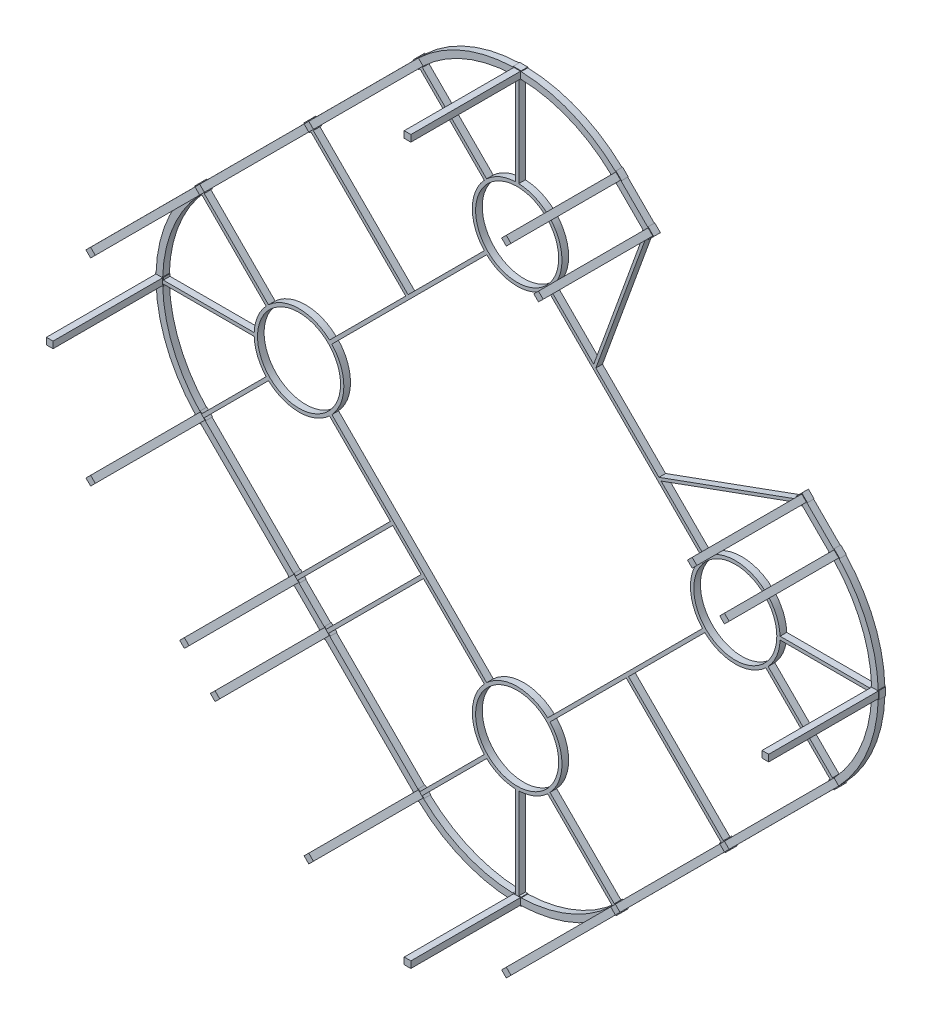
SolidWorks part; units mm, degrees
material "PET"
ref_plane "Front Plane" through (0, 0, 0) normal (0, 0, 1) x (1, 0, 0)
ref_plane "Top Plane" through (0, 0, 0) normal (0, 1, 0) x (1, 0, 0)
ref_plane "Right Plane" through (0, 0, 0) normal (1, 0, 0) x (0, 0, -1)
sketch "Sketch1" plane through (0, 0, 0) normal (0, 0, 1) x (1, 0, 0)
  line L96 (-31.2949, 95.2721) -> (-62.435, 64.132)
  line L97 (-95.2719, -31.2952) -> (-68.7516, -57.8154)
  line L98 (95.2742, -31.2929) -> (64.132, -62.435)
  line L99 (31.2931, 95.274) -> (39.3012, 87.2658)
  line L102 (95.4168, -28.0415) -> (95.5445, -28.1692)
  line L103 (-62.5717, 60.8746) -> (-62.7178, 61.0208)
  line L105 (-60.8746, 62.5717) -> (-61.0208, 62.7178)
  line L108 (-106.5251, 1.2) -> (-106.7143, 1.2)
  line L110 (-106.5251, -1.2) -> (-106.7143, -1.2)
  line L111 (-1.2, -106.5251) -> (-1.2, -106.7143)
  line L112 (1.2, -106.5251) -> (1.2, -106.7143)
  line L113 (60.8746, -62.5717) -> (61.0208, -62.7178)
  line L114 (62.5717, -60.8746) -> (62.7178, -61.0208)
  line L115 (106.5251, -1.2) -> (106.7143, -1.2)
  line L118 (106.5251, 1.2) -> (106.7143, 1.2)
  line L121 (93.7188, 29.7348) -> (93.8631, 29.8791)
  line L122 (95.4159, 28.0378) -> (95.5458, 28.1677)
  line L123 (29.7354, 93.7161) -> (29.8789, 93.8597)
  line L124 (28.0383, 95.4131) -> (28.1694, 95.5443)
  line L125 (-1.2, 106.5251) -> (-1.2, 106.7143)
  line L126 (1.2, 106.5251) -> (1.2, 106.7143)
  line L127 (93.7198, -29.7386) -> (93.8599, -29.8787)
  line L128 (-106.7272, -1) -> (-108.7272, -1)
  line L137 (-106.7272, 1) -> (-108.7272, 1)
  line L138 (-95.411, 28.3121) -> (-96.8252, 29.7262)
  line L139 (-93.9969, 29.7264) -> (-95.4111, 31.1406)
  line L140 (-93.7194, 29.7317) -> (-93.8631, 29.8755)
  line L141 (-95.4164, 28.0346) -> (-95.5476, 28.1659)
  line L142 (-61.1589, 62.5731) -> (-62.5731, 63.9873)
  line L143 (-62.5731, 61.1589) -> (-63.9874, 62.5731)
  line L144 (-28.3184, 95.4068) -> (-29.7326, 96.821)
  line L145 (-28.041, 95.4122) -> (-28.1713, 95.5425)
  line L146 (-29.7327, 93.9927) -> (-31.1469, 95.4069)
  line L147 (-29.738, 93.7152) -> (-29.8807, 93.8579)
  line L149 (-1, 106.7272) -> (-1, 108.7272)
  line L150 (1, 106.7272) -> (1, 108.7272)
  line L152 (28.3157, 95.4078) -> (29.7299, 96.822)
  line L153 (29.73, 93.9937) -> (31.1442, 95.4079)
  line L154 (39.4263, 84.2797) -> (40.8406, 85.6939)
  line L155 (38.0121, 85.6939) -> (39.4263, 87.1081)
  line L156 (37.7278, 85.6924) -> (37.887, 85.8516)
  line L157 (84.282, 39.4255) -> (85.6962, 40.8397)
  line L158 (85.6948, 37.727) -> (85.8547, 37.8869)
  line L159 (85.6963, 38.0113) -> (87.1105, 39.4256)
  line L160 (93.9963, 29.7295) -> (95.4105, 31.1437)
  line L161 (95.4105, 28.3152) -> (96.8247, 29.7294)
  line L162 (106.7272, -1) -> (108.7272, -1)
  line L163 (106.7272, 1) -> (108.7272, 1)
  line L164 (93.9973, -29.7332) -> (95.4116, -31.1474)
  line L165 (95.4114, -28.3189) -> (96.8257, -29.7331)
  line L166 (62.5731, -61.1589) -> (63.9874, -62.5731)
  line L167 (61.1589, -62.5731) -> (62.5731, -63.9873)
  line L168 (29.7331, -93.9995) -> (31.1473, -95.4137)
  line L169 (28.3189, -95.4137) -> (29.7331, -96.8279)
  line L170 (-1, -106.7272) -> (-1, -108.7272)
  line L179 (1, -106.7272) -> (1, -108.7272)
  line L180 (-29.7296, -94.0005) -> (-31.1438, -95.4148)
  line L181 (-28.3153, -95.4146) -> (-29.7294, -96.8289)
  line L182 (-56.5346, -67.1881) -> (-57.9488, -68.6023)
  line L183 (-57.9488, -65.7738) -> (-59.3631, -67.1881)
  line L184 (-67.188, -56.5346) -> (-68.6023, -57.9489)
  line L185 (-65.7738, -57.9489) -> (-67.188, -59.3631)
  line L186 (-95.4154, -28.0446) -> (-95.5423, -28.1715)
  line L187 (-95.41, -28.3221) -> (-96.8243, -29.7363)
  line L188 (-93.9959, -29.7363) -> (-95.4101, -31.1505)
  line L189 (-93.7184, -29.7417) -> (-93.8577, -29.8809)
  line L190 (0, 65.6738) -> (29.0324, 94.7062) construction
  line L191 (0, 65.6738) -> (0, 106.7318) construction
  line L192 (0, 65.6738) -> (-9.5459, 75.2198) construction
  line L193 (27.2253, 93.6061) -> (27.9324, 92.899) construction
  line L194 (-0.5, 103.688) -> (0.5, 103.688) construction
  line L195 (94.9235, -28.5426) -> (75.5667, -9.1858)
  line L196 (29.2463, 94.213) -> (9.8929, 74.8596)
  line L197 (28.5392, 94.9201) -> (9.1858, 75.5667)
  line L198 (94.2164, -29.2497) -> (74.8596, -9.8929)
  line L199 (0.5, 106.5306) -> (0.5, 79.1645)
  line L200 (-0.5, 106.5306) -> (-0.5, 79.1645)
  line L201 (1.2, 108.7151) -> (1.2, 108.9252)
  line L202 (106.5306, -0.5) -> (79.1645, -0.5)
  line L203 (106.5306, 0.5) -> (79.1645, 0.5)
  line L204 (-28.5399, 94.9212) -> (-9.1858, 75.5667)
  line L205 (-29.2471, 94.2139) -> (-9.8928, 74.8597)
  line L206 (94.9214, 28.5401) -> (75.5667, 9.1858)
  line L207 (94.2141, 29.2473) -> (74.8597, 9.8928)
  line L208 (-28.5424, -94.9233) -> (-9.1858, -75.5667)
  line L209 (-29.2495, -94.2162) -> (-9.8929, -74.8596)
  line L210 (-0.5, -106.5306) -> (-0.5, -79.1645)
  line L211 (0.5, -106.5306) -> (0.5, -79.1645)
  line L212 (28.5435, -94.9248) -> (9.1858, -75.5667)
  line L213 (29.2507, -94.2176) -> (9.8928, -74.8597)
  line L214 (-94.9199, 28.539) -> (-75.5667, 9.1858)
  line L223 (-94.2127, 29.2461) -> (-74.8596, 9.8929)
  line L224 (-106.5306, 0.5) -> (-79.1645, 0.5)
  line L225 (-106.5306, -0.5) -> (-79.1645, -0.5)
  line L226 (-94.9246, -28.5433) -> (-75.5667, -9.1858)
  line L227 (-94.2174, -29.2505) -> (-74.8597, -9.8928)
  line L228 (0, 65.6738) -> (-65.6738, 0) construction
  line L229 (-34.1935, 32.1874) -> (-33.4863, 31.4803) construction
  line L230 (-33.4863, 31.4803) -> (-55.7808, 9.1858)
  line L231 (-34.1935, 32.1874) -> (-56.4879, 9.8929)
  line L232 (-34.1935, 32.1874) -> (-33.544, 32.8369)
  line L233 (-33.4863, 31.4803) -> (-9.1858, 55.7808)
  line L234 (-32.8369, 32.8369) -> (-61.8693, 61.8693) construction
  line L235 (-32.8369, 33.544) -> (-9.8929, 56.4879)
  line L236 (-32.8369, 33.544) -> (-61.3735, 62.0806)
  line L237 (-33.544, 32.8369) -> (-62.0806, 61.3735)
  line L238 (0, 0) -> (35.109, 35.109) construction
  line L239 (31.4803, -33.4863) -> (9.1858, -55.7808)
  line L240 (32.1874, -34.1935) -> (9.8929, -56.4879)
  line L241 (31.4803, -33.4863) -> (55.7808, -9.1858)
  line L242 (32.1874, -34.1935) -> (32.8369, -33.544)
  line L243 (33.544, -32.8369) -> (62.0806, -61.3735)
  line L244 (32.8369, -33.544) -> (61.3735, -62.0806)
  line L245 (-96.9625, 29.5806) -> (-97.1135, 29.7317)
  line L246 (-38.1636, -28.2173) -> (-56.4879, -9.8929)
  line L247 (56.4879, 9.8929) -> (43.3373, 23.0436)
  line L248 (-66.4842, -57.245) -> (-37.81, -28.5708) construction
  line L249 (-52.5007, -42.5544) -> (-51.7936, -43.2615) construction
  line L250 (-28.2173, -38.1636) -> (-56.7492, -66.6955)
  line L251 (-28.9244, -37.4565) -> (-57.4563, -65.9884)
  line L252 (-37.4565, -28.9244) -> (-65.9884, -57.4563)
  line L253 (-38.1636, -28.2173) -> (-66.6955, -56.7492)
  line L254 (-65.4895, -57.9474) -> (-65.6404, -58.0982)
  line L255 (-67.1866, -56.2503) -> (-67.3374, -56.4012)
  line L256 (-57.9474, -65.4895) -> (-58.0982, -65.6404)
  line L257 (-56.2503, -67.1866) -> (-56.4012, -67.3374)
  line L258 (-29.7349, -93.723) -> (-29.8753, -93.8633)
  line L259 (-28.0378, -95.42) -> (-28.1656, -95.5478)
  line L260 (28.0414, -95.4191) -> (28.168, -95.5456)
  line L261 (29.7385, -93.722) -> (29.8775, -93.8611)
  line L262 (-55.7808, -9.1859) -> (-9.1859, -55.7809)
  line L263 (-28.9244, -37.4565) -> (-37.4565, -28.9244)
  line L264 (-9.8929, -56.4879) -> (-28.2173, -38.1636)
  line L265 (9.1859, 55.7809) -> (55.7808, 9.1859)
  line L266 (-95.2774, 31.2897) -> (-95.4165, 31.4288)
  line L267 (-93.8631, 29.8755) -> (-62.7178, 61.0208)
  line L268 (-96.1204, 30.4466) -> (-95.4111, 31.1406)
  line L269 (-95.411, 28.3121) -> (-93.9969, 29.7264)
  line L270 (-61.0208, 62.7178) -> (-29.8807, 93.8579)
  line L271 (-62.435, 64.132) -> (-62.5717, 64.2688)
  line L272 (-64.132, 62.435) -> (-95.2774, 31.2897)
  line L273 (-64.132, 62.435) -> (-64.2688, 62.5717)
  line L274 (-62.5764, 61.1622) -> (-61.1622, 62.5764)
  line L275 (-63.9874, 62.5731) -> (-62.5731, 63.9873)
  line L276 (-31.2949, 95.2721) -> (-31.4351, 95.4123)
  line L277 (-29.5861, 96.9573) -> (-29.7381, 97.1093)
  line L278 (-31.1469, 95.4069) -> (-29.7326, 96.821)
  line L279 (-29.7327, 93.9927) -> (-28.3184, 95.4068)
  line L280 (-1.2, 108.7151) -> (-1.2, 108.9252)
  line L281 (-1, 106.7272) -> (1, 106.7272)
  line L282 (29.5841, 96.9591) -> (29.7353, 97.1103)
  line L283 (31.2931, 95.274) -> (31.4324, 95.4133)
  line L284 (29.8789, 93.8597) -> (37.887, 85.8516)
  line L285 (28.3157, 95.4078) -> (29.73, 93.9937)
  line L286 (29.7299, 96.822) -> (31.1442, 95.4079)
  line L287 (39.3012, 87.2658) -> (39.4249, 87.3895)
  line L288 (38.0121, 85.6939) -> (39.4263, 84.2797)
  line L289 (40.8406, 85.6939) -> (39.4263, 87.1081)
  line L290 (87.2674, 39.2997) -> (87.3919, 39.4242)
  line L291 (87.2674, 39.2997) -> (95.2755, 31.2915)
  line L292 (85.8547, 37.8869) -> (93.8631, 29.8791)
  line L293 (84.282, 39.4255) -> (85.6963, 38.0113)
  line L294 (85.6962, 40.8397) -> (87.1105, 39.4256)
  line L295 (93.9963, 29.7295) -> (95.4105, 28.3152)
  line L296 (96.8247, 29.7294) -> (95.4105, 31.1437)
  line L297 (95.2755, 31.2915) -> (95.4159, 31.4319)
  line L298 (96.9606, 29.5825) -> (97.113, 29.7349)
  line L299 (108.7151, 1.2) -> (108.9252, 1.2)
  line L300 (108.7151, -1.2) -> (108.9252, -1.2)
  line L301 (106.7272, -1) -> (106.7272, 1)
  line L302 (93.8599, -29.8787) -> (62.7178, -61.0208)
  line L303 (93.9973, -29.7332) -> (95.4114, -28.3189)
  line L304 (95.4116, -31.1474) -> (96.8257, -29.7331)
  line L305 (96.9593, -29.5839) -> (97.1139, -29.7385)
  line L306 (95.2742, -31.2929) -> (95.4169, -31.4356)
  line L307 (64.132, -62.435) -> (64.2688, -62.5717)
  line L308 (62.435, -64.132) -> (62.5717, -64.2688)
  line L309 (61.0208, -62.7178) -> (29.8775, -93.8611)
  line L310 (62.435, -64.132) -> (31.2917, -95.2753)
  line L311 (62.5764, -61.1622) -> (61.1622, -62.5764)
  line L312 (62.5731, -63.9873) -> (63.9874, -62.5731)
  line L313 (31.2917, -95.2753) -> (31.4356, -95.4191)
  line L314 (29.5828, -96.9604) -> (29.7385, -97.1162)
  line L315 (28.3189, -95.4137) -> (29.7331, -93.9995)
  line L316 (29.7331, -96.8279) -> (31.1473, -95.4137)
  line L317 (1.2, -108.7151) -> (1.2, -108.9252)
  line L318 (-1.2, -108.7151) -> (-1.2, -108.9252)
  line L319 (-1, -106.7272) -> (1, -106.7272)
  line L320 (-29.5804, -96.9627) -> (-29.7349, -97.1171)
  line L321 (-31.2894, -95.2776) -> (-31.432, -95.4201)
  line L322 (-29.7296, -94.0005) -> (-28.3153, -95.4146)
  line L323 (-29.7294, -96.8289) -> (-31.1438, -95.4148)
  line L324 (-57.9488, -65.7738) -> (-56.5346, -67.1881)
  line L325 (-56.4012, -67.3374) -> (-29.8753, -93.8633)
  line L326 (-57.8154, -68.7516) -> (-31.2894, -95.2776)
  line L327 (-59.5124, -67.0546) -> (-59.6445, -67.1866)
  line L328 (-57.8154, -68.7516) -> (-57.9474, -68.8837)
  line L329 (-57.9488, -68.6023) -> (-59.3631, -67.1881)
  line L330 (-68.7516, -57.8154) -> (-68.8837, -57.9474)
  line L331 (-67.0546, -59.5124) -> (-67.1866, -59.6445)
  line L332 (-65.6404, -58.0982) -> (-58.0982, -65.6404)
  line L333 (-68.6023, -57.9489) -> (-67.188, -59.3631)
  line L334 (-67.0546, -59.5124) -> (-59.5124, -67.0546)
  line L335 (-67.188, -56.5346) -> (-65.7738, -57.9489)
  line L336 (-96.9571, -29.5863) -> (-97.1125, -29.7417)
  line L337 (-93.8577, -29.8809) -> (-67.3374, -56.4012)
  line L338 (-95.41, -28.3221) -> (-93.9959, -29.7363)
  line L339 (-95.4101, -31.1505) -> (-96.8243, -29.7363)
  line L340 (-95.2719, -31.2952) -> (-95.4155, -31.4388)
  line L341 (-108.7151, -1.2) -> (-108.9252, -1.2)
  line L342 (-108.7151, 1.2) -> (-108.9252, 1.2)
  line L343 (-108.7272, -1) -> (-108.7272, 1)
  line L344 (-106.7272, 1) -> (-106.7272, -1)
  line L345 (108.7272, 1) -> (108.7272, -1)
  line L346 (33.544, -32.8369) -> (56.4879, -9.8929)
  line L347 (38.5811, 84.8487) -> (23.3679, 43.013) construction
  line L348 (37.9483, 84.3245) -> (38.7294, 84.0405) construction
  line L349 (37.9483, 84.3245) -> (38.2564, 85.1719)
  line L350 (38.2564, 85.1719) -> (23.0436, 43.3373)
  line L351 (39.4249, 83.9954) -> (41.122, 85.6925)
  line L352 (83.9977, 39.424) -> (85.6948, 41.1212)
  line L353 (38.905, 84.5233) -> (23.6922, 42.6887)
  line L354 (85.1719, 38.2564) -> (43.3373, 23.0436)
  line L355 (84.5233, 38.905) -> (42.6887, 23.6922)
  line L356 (42.6887, 23.6922) -> (23.6922, 42.6887)
  line L357 (23.0436, 43.3373) -> (9.8929, 56.4879)
  line L358 (83.9977, 39.424) -> (84.5233, 38.905)
  line L359 (85.1719, 38.2564) -> (85.6948, 37.727)
  arc A156 (-96.1204, 30.4466) -> (-96.8247, 29.7257) centre (-65.6738, 0) ccw
  arc A157 (-28.1656, -95.5478) -> (-1.2, -106.7143) centre (0, -65.6738) ccw
  arc A158 (95.5445, -28.1692) -> (106.7143, -1.2) centre (65.6738, 0) ccw
  arc A159 (29.5841, 96.9591) -> (1.2, 108.7151) centre (0, 65.6738) ccw
  arc A160 (28.1694, 95.5443) -> (1.2, 106.7143) centre (0, 65.6738) ccw
  arc A161 (95.4169, -31.4356) -> (97.1139, -29.7385) centre (18.534, 47.1392) ccw
  arc A162 (-60.8746, 62.5717) -> (-61.3735, 62.0806) centre (14.3086, -14.3086) ccw
  arc A163 (-62.5717, 64.2688) -> (-64.2688, 62.5717) centre (14.3086, -14.3086) ccw
  arc A164 (-108.9252, 1.2) -> (-108.9252, -1.2) centre (1, 0) ccw
  arc A165 (-106.5251, 1.2) -> (-106.5306, 0.5) centre (1, 0) ccw
  arc A166 (-1.2, -106.5251) -> (-0.5, -106.5306) centre (0, 1) ccw
  arc A167 (-1.2, -108.9252) -> (1.2, -108.9252) centre (0, 1) ccw
  arc A168 (60.8746, -62.5717) -> (61.3735, -62.0806) centre (-14.3086, 14.3086) ccw
  arc A169 (62.5717, -64.2688) -> (64.2688, -62.5717) centre (-14.3086, 14.3086) ccw
  arc A170 (106.5251, -1.2) -> (106.5306, -0.5) centre (-1, 0) ccw
  arc A171 (108.9252, -1.2) -> (108.9252, 1.2) centre (-1, 0) ccw
  arc A172 (95.4159, 28.0378) -> (94.9214, 28.5401) centre (18.5356, -47.1454) ccw
  arc A173 (97.113, 29.7349) -> (95.4159, 31.4319) centre (18.5356, -47.1454) ccw
  arc A174 (29.7354, 93.7161) -> (29.2463, 94.213) centre (-47.1424, 18.5304) ccw
  arc A175 (31.4324, 95.4133) -> (29.7353, 97.1103) centre (-47.1424, 18.5304) ccw
  arc A176 (1.2, 106.5251) -> (0.5, 106.5306) centre (0, -1) ccw
  arc A177 (1.2, 108.9252) -> (-1.2, 108.9252) centre (0, -1) ccw
  arc A178 (93.7198, -29.7386) -> (94.2164, -29.2497) centre (18.534, 47.1392) ccw
  arc A179 (-93.7194, 29.7317) -> (-94.2127, 29.2461) centre (-18.5336, -47.1461) ccw
  arc A180 (-95.4165, 31.4288) -> (-97.1135, 29.7317) centre (-18.5336, -47.1461) ccw
  arc A181 (-28.041, 95.4122) -> (-28.5399, 94.9212) centre (47.1422, 18.532) ccw
  arc A182 (-29.7381, 97.1093) -> (-31.4351, 95.4123) centre (47.1422, 18.532) ccw
  arc A183 (39.4249, 83.9954) -> (38.905, 84.5233) centre (-37.4554, 8.8122) ccw
  arc A184 (41.122, 85.6925) -> (39.4249, 87.3895) centre (-37.4554, 8.8122) ccw
  arc A185 (87.3919, 39.4242) -> (85.6948, 41.1212) centre (8.8171, -37.4587) ccw
  arc A186 (-97.1125, -29.7417) -> (-95.4155, -31.4388) centre (-18.5352, 47.1386) ccw
  arc A187 (-95.4154, -28.0446) -> (-94.9246, -28.5433) centre (-18.5352, 47.1386) ccw
  circle A188 centre (0, 65.6738) radius 12.5
  arc A189 (-9.1858, 55.7808) -> (9.1859, 55.7809) centre (0, 65.6738) ccw
  arc A190 (79.1645, 0.5) -> (75.5667, 9.1858) centre (65.6738, 0) ccw
  circle A191 centre (65.6738, 0) radius 12.5
  arc A192 (9.1858, -55.7808) -> (-9.1859, -55.7809) centre (0, -65.6738) ccw
  circle A193 centre (0, -65.6738) radius 12.5
  arc A194 (-55.7808, -9.1859) -> (-55.7808, 9.1858) centre (-65.6738, 0) ccw
  circle A195 centre (-65.6738, 0) radius 12.5
  arc A196 (-68.8837, -57.9474) -> (-67.1866, -59.6445) centre (9.6937, 18.9329) ccw
  arc A197 (-67.1866, -56.2503) -> (-66.6955, -56.7492) centre (9.6937, 18.9329) ccw
  arc A198 (-59.6445, -67.1866) -> (-57.9474, -68.8837) centre (18.9329, 9.6937) ccw
  arc A199 (-57.9474, -65.4895) -> (-57.4563, -65.9884) centre (18.9329, 9.6937) ccw
  arc A200 (-31.432, -95.4201) -> (-29.7349, -97.1171) centre (47.1428, -18.5372) ccw
  arc A201 (-29.7349, -93.723) -> (-29.2495, -94.2162) centre (47.1428, -18.5372) ccw
  arc A202 (28.0414, -95.4191) -> (28.5435, -94.9248) centre (-47.1418, -18.5388) ccw
  arc A203 (29.7385, -97.1162) -> (31.4356, -95.4191) centre (-47.1418, -18.5388) ccw
  arc A204 (-96.9625, 29.5806) -> (-108.7151, 1.2) centre (-65.6738, 0) ccw
  arc A205 (-95.5476, 28.1659) -> (-106.7143, 1.2) centre (-65.6738, 0) ccw
  arc A206 (-94.9199, 28.539) -> (-95.4164, 28.0346) centre (-18.5336, -47.1461) ccw
  arc A207 (-62.0806, 61.3735) -> (-62.5717, 60.8746) centre (14.3086, -14.3086) ccw
  arc A208 (-29.2471, 94.2139) -> (-29.738, 93.7152) centre (47.1422, 18.532) ccw
  arc A209 (-1.2, 108.7151) -> (-29.5861, 96.9573) centre (0, 65.6738) ccw
  arc A210 (1, 108.7202) -> (-1, 108.7202) centre (0, 65.6738) ccw
  arc A211 (28.5392, 94.9201) -> (28.0383, 95.4131) centre (-47.1424, 18.5304) ccw
  arc A212 (-1.2, 106.7143) -> (-28.1713, 95.5425) centre (0, 65.6738) ccw
  arc A213 (-0.5, 106.5306) -> (-1.2, 106.5251) centre (0, -1) ccw
  arc A214 (94.2141, 29.2473) -> (93.7188, 29.7348) centre (18.5356, -47.1454) ccw
  arc A215 (75.5667, -9.1858) -> (79.1645, -0.5) centre (65.6738, 0) ccw
  arc A216 (108.7151, 1.2) -> (96.9606, 29.5825) centre (65.6738, 0) ccw
  arc A217 (106.7143, 1.2) -> (95.5458, 28.1677) centre (65.6738, 0) ccw
  arc A218 (106.5306, 0.5) -> (106.5251, 1.2) centre (-1, 0) ccw
  arc A219 (94.9235, -28.5426) -> (95.4168, -28.0415) centre (18.534, 47.1392) ccw
  arc A220 (96.9593, -29.5839) -> (108.7151, -1.2) centre (65.6738, 0) ccw
  arc A221 (62.0806, -61.3735) -> (62.5717, -60.8746) centre (-14.3086, 14.3086) ccw
  arc A222 (29.2507, -94.2176) -> (29.7385, -93.722) centre (-47.1418, -18.5388) ccw
  arc A223 (0.5, -106.5306) -> (1.2, -106.5251) centre (0, 1) ccw
  arc A224 (1.2, -106.7143) -> (28.168, -95.5456) centre (0, -65.6738) ccw
  arc A225 (-1, -108.7202) -> (1, -108.7202) centre (0, -65.6738) ccw
  arc A226 (1.2, -108.7151) -> (29.5828, -96.9604) centre (0, -65.6738) ccw
  arc A227 (-28.5424, -94.9233) -> (-28.0378, -95.42) centre (47.1428, -18.5372) ccw
  arc A228 (-29.5804, -96.9627) -> (-1.2, -108.7151) centre (0, -65.6738) ccw
  arc A229 (-56.7492, -66.6955) -> (-56.2503, -67.1866) centre (18.9329, 9.6937) ccw
  arc A230 (-65.9884, -57.4563) -> (-65.4895, -57.9474) centre (9.6937, 18.9329) ccw
  arc A231 (-94.2174, -29.2505) -> (-93.7184, -29.7417) centre (-18.5352, 47.1386) ccw
  arc A232 (-106.7143, -1.2) -> (-95.5423, -28.1715) centre (-65.6738, 0) ccw
  arc A233 (-106.5306, -0.5) -> (-106.5251, -1.2) centre (1, 0) ccw
  arc A234 (-108.7151, -1.2) -> (-96.9571, -29.5863) centre (-65.6738, 0) ccw
  arc A235 (56.4879, -9.8929) -> (74.8596, -9.8929) centre (65.6738, 0) ccw
  arc A236 (55.7808, 9.1859) -> (55.7808, -9.1858) centre (65.6738, 0) ccw
  arc A237 (74.8597, 9.8928) -> (56.4879, 9.8929) centre (65.6738, 0) ccw
  arc A238 (9.8928, -74.8597) -> (9.8929, -56.4879) centre (0, -65.6738) ccw
  arc A239 (0.5, -79.1645) -> (9.1858, -75.5667) centre (0, -65.6738) ccw
  arc A240 (-9.1858, -75.5667) -> (-0.5, -79.1645) centre (0, -65.6738) ccw
  arc A241 (-9.8929, -56.4879) -> (-9.8929, -74.8596) centre (0, -65.6738) ccw
  arc A242 (-74.8597, -9.8928) -> (-56.4879, -9.8929) centre (-65.6738, 0) ccw
  arc A243 (-79.1645, -0.5) -> (-75.5667, -9.1858) centre (-65.6738, 0) ccw
  arc A244 (-75.5667, 9.1858) -> (-79.1645, 0.5) centre (-65.6738, 0) ccw
  arc A245 (-56.4879, 9.8929) -> (-74.8596, 9.8929) centre (-65.6738, 0) ccw
  arc A246 (9.8929, 56.4879) -> (9.8929, 74.8596) centre (0, 65.6738) ccw
  arc A247 (9.1858, 75.5667) -> (0.5, 79.1645) centre (0, 65.6738) ccw
  arc A248 (-0.5, 79.1645) -> (-9.1858, 75.5667) centre (0, 65.6738) ccw
  arc A249 (-9.8928, 74.8597) -> (-9.8929, 56.4879) centre (0, 65.6738) ccw
  arc A250 (38.2564, 85.1719) -> (37.7278, 85.6924) centre (-37.4554, 8.8122) ccw
  point P157 (27.5788, 93.2526)
  point P165 (0, 103.688)
  point P224 (-33.8399, 31.8339)
  point P233 (-32.8369, 32.8369)
  point P252 (-52.1471, -42.9079)
  point P294 (38.3389, 84.1825)
  dimension "D1" = 25
  dimension "D2" = 1
  dimension "D3" = 1
  dimension "D4" = 1
  dimension "D5" = 1
  dimension "D6" = 6.0331
  dimension "D7" = 1
  dimension "D8" = 0.8312
extrude "Boss-Extrude1" add sketch "Sketch1" against normal blind 2 contours L293 | L303 | L180 | L335 region at (-31.1472, 95.56, 0) region at (85.6962, 39.4255, 0) region at (-29.7295, -95.4147, 0)
extrude "Boss-Extrude2" add sketch "Sketch1<4>" along normal blind 35 from offset 2 contours L268 A156 L138 L269 L139 | L275 L143 L274 L142 | L146 L279 L144 L278 | L150 A210 L149 L281 | L286 L152 L285 L153 | L154 L289 L155 L288 | L294 L157 L293 L159 | L161 L296 L160 L295 | L345 L163 L301 L162 | L164 L304 L165 L303 | L167 L312 L166 L311 | L169 L316 L168 L315 | L170 A225 L179 L319 | L323 L181 L322 L180 | L329 L182 L324 L183 | L335 L184 L333 L185 | L339 L188 L338 L187 | L344 L137 L343 L128 region at (-107.7272, 0, 0) region at (-95.4134, 29.7284, 0) region at (-62.5748, 62.5748, 0) region at (-29.7327, 95.4069, 0) region at (0, 107.7276, 0) region at (29.73, 95.4078, 0) region at (39.4263, 85.6939, 0) region at (85.6962, 39.4255, 0) region at (95.4105, 29.7295, 0) region at (107.7272, 0, 0) region at (95.4115, -29.7332, 0) region at (62.5748, -62.5748, 0) region at (29.7331, -95.4137, 0) region at (0, -107.7276, 0) region at (-29.7295, -95.4147, 0) region at (-57.9488, -67.1881, 0) region at (-67.188, -57.9489, 0) region at (-95.4101, -29.7363, 0) offset against normal yes
sketch "Sketch1<4>" plane through (0, 0, 0) normal (0, 0, 1) x (1, 0, 0) same geometry as "Sketch1"
